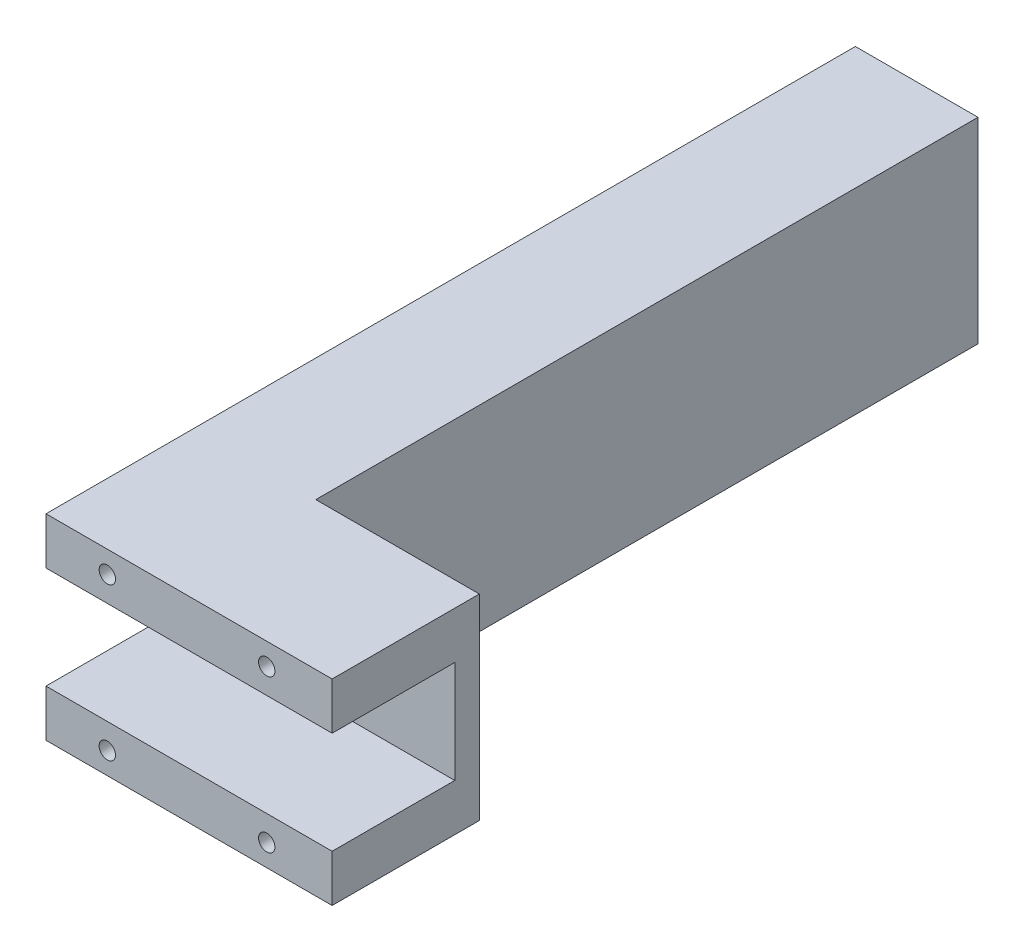
SolidWorks part; units mm, degrees
ref_plane "Alzado" through (0, 0, 0) normal (0, 0, 1) x (1, 0, 0)
ref_plane "Planta" through (0, 0, 0) normal (0, 1, 0) x (1, 0, 0)
ref_plane "Vista lateral" through (0, 0, 0) normal (1, 0, 0) x (0, 0, -1)
sketch "Croquis1" plane through (0, 0, 0) normal (0, 0, 1) x (1, 0, 0)
  line L1 (-66.2162, 31.0113) -> (3.7838, 31.0113)
  line L2 (-66.2162, 31.0113) -> (-66.2162, -16.9887)
  line L3 (-66.2162, -16.9887) -> (3.7838, -16.9887)
  line L4 (3.7838, 31.0113) -> (3.7838, -16.9887)
  dimension "D1" = 48
  dimension "D2" = 70
extrude "Saliente-Extruir1" add sketch "Croquis1" along normal blind 6
sketch "Croquis4" plane through (0, 0, 6) normal (0, 0, 1) x (1, 0, 0)
  line L0 (-66.2162, 31.0113) -> (-66.2162, 19.5113)
  line L1 (-66.2162, 31.0113) -> (-66.2162, -16.9887) construction
  line L3 (-66.2162, -5.4887) -> (-66.2162, -16.9887)
  line L4 (-66.2162, 31.0113) -> (3.7838, 31.0113)
  line L6 (3.7838, 31.0113) -> (3.7838, 19.5113)
  line L7 (3.7838, -16.9887) -> (3.7838, 31.0113) construction
  line L8 (3.7838, 19.5113) -> (-66.2162, 19.5113)
  line L9 (-66.2162, -5.4887) -> (3.7838, -5.4887)
  line L10 (3.7838, -5.4887) -> (3.7838, -16.9887)
  line L11 (3.7838, -16.9887) -> (-66.2162, -16.9887)
  dimension "D1" = 25
extrude "Saliente-Extruir3" add sketch "Croquis4" along normal blind 30
sketch "Croquis3" plane through (0, 0, 6) normal (0, 0, 1) x (1, 0, 0)
  circle A0 centre (-51.2162, 25.6613) radius 2.125
  circle A1 centre (-12.2162, 25.6613) radius 2.125
  circle A2 centre (-12.2162, -11.6387) radius 2.125
  circle A3 centre (-51.2162, -11.6387) radius 2.125
  dimension "D7" = 4.25
  dimension "D9" = 4.25
  dimension "D10" = 4.25
  dimension "D2" = 4.25
  dimension "D3" = 37.3
  dimension "D4" = 39
sketch "Croquis5" plane through (0, 0, 36) normal (0, 0, 1) x (1, 0, 0)
  circle A0 centre (-51.2162, 25.6613) radius 2
  circle A1 centre (-12.2162, 25.6613) radius 2
  circle A2 centre (-12.2162, -11.6387) radius 2
  circle A3 centre (-51.2162, -11.6387) radius 2
  dimension "D1" = 4
  dimension "D2" = 4
  dimension "D3" = 4
  dimension "D4" = 4
extrude "Cortar-Extruir3" cut sketch "Croquis5" against normal blind 16
sketch "Croquis6" plane through (0, 0, 0) normal (0, 0, -1) x (-1, 0, 0)
  line L0 (66.2162, -16.9887) -> (-3.7838, -16.9887) construction
  line L1 (66.2162, 31.0113) -> (36.2162, 31.0113)
  line L2 (66.2162, 31.0113) -> (66.2162, -16.9887)
  line L3 (66.2162, -16.9887) -> (36.2162, -16.9887)
  line L4 (36.2162, 31.0113) -> (36.2162, -16.9887)
  dimension "D1" = 30
extrude "Saliente-Extruir4" add sketch "Croquis6" along normal blind 162
sketch "Croquis7" plane through (0, 0, -162) normal (0, 0, -1) x (-1, 0, 0)
  circle A0 centre (51.2162, 7.0113) radius 2
  dimension "D1" = 4
extrude "Cortar-Extruir4" cut sketch "Croquis7" against normal blind 16
sketch "Croquis8" plane through (0, 0, -162) normal (0, 0, -1) x (-1, 0, 0)
  line L0 (41.2162, 12.0113) -> (41.2162, 9.5131)
  line L10 (36.2162, 12.0113) -> (41.2162, 12.0113)
  line L11 (36.2162, 12.0113) -> (36.2162, 2.0113)
  line L12 (36.2162, 2.0113) -> (41.2162, 2.0113)
  line L21 (41.2162, 9.5131) -> (44.2162, 9.5131)
  line L23 (41.2162, 4.5131) -> (44.2162, 4.5131)
  line L24 (44.2162, 9.5131) -> (44.2162, 4.5131)
  line L25 (41.2162, 2.0113) -> (41.2162, 4.5131)
  dimension "D1" = 5
  dimension "D2" = 3
  dimension "D3" = 5
